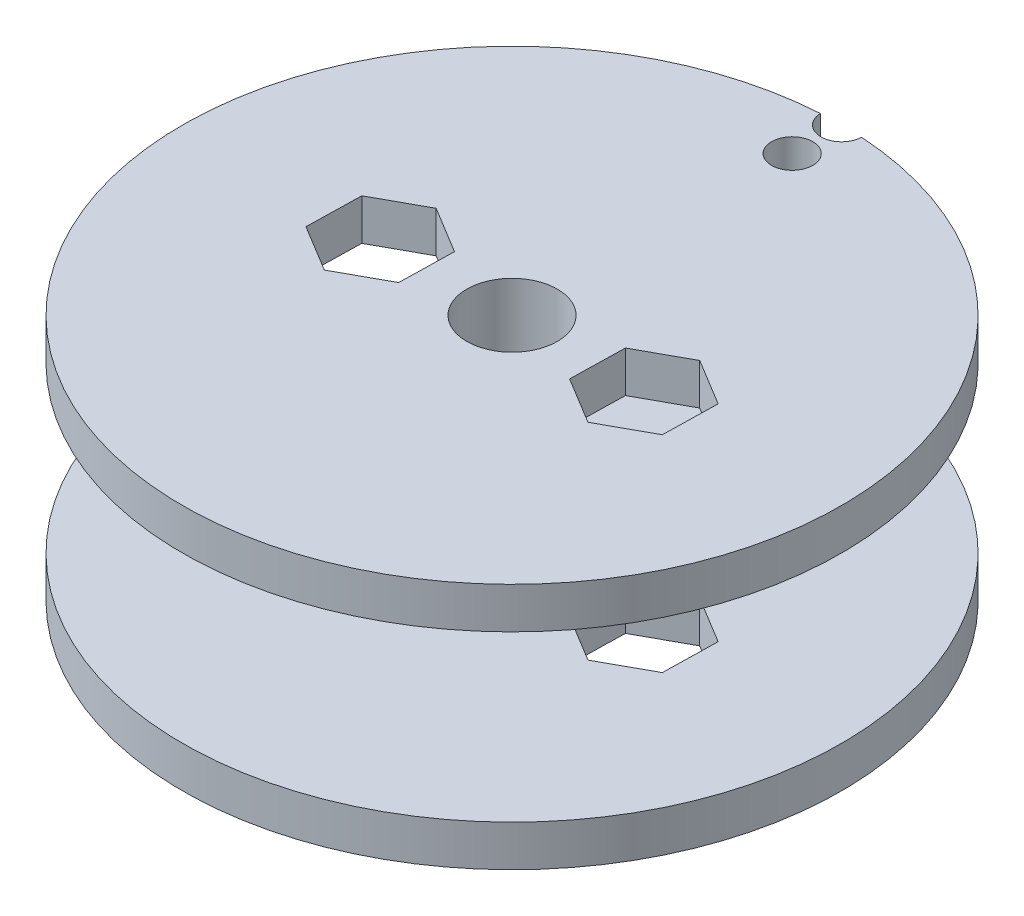
SolidWorks part; units mm, degrees
ref_plane "Front Plane" through (0, 0, 0) normal (0, 0, 1) x (1, 0, 0)
ref_plane "Top Plane" through (0, 0, 0) normal (0, 1, 0) x (1, 0, 0)
ref_plane "Right Plane" through (0, 0, 0) normal (1, 0, 0) x (0, 0, -1)
sketch "Sketch1" plane through (0, 0, 0) normal (0, 1, 0) x (1, 0, 0)
  circle A1 centre (0, 0) radius 20
  circle A2 centre (0, 0) radius 2.75
extrude "Boss-Extrude1" add sketch "Sketch1" along normal blind 2.5
sketch "Sketch2" plane through (0, 2.5, 0) normal (0, 1, 0) x (1, 0, 0)
  circle A0 centre (0, 0) radius 3
  circle A1 centre (0, 0) radius 2.75
sketch "Sketch3" plane through (0, 0, 0) normal (0, -1, 0) x (1, 0, 0)
  line L0 (-5.1613, 1.7213) -> (-8.0713, 3.319)
  line L1 (5.1613, -1.7213) -> (8.0713, -3.319)
  line L2 (8.0713, -3.319) -> (10.91, -1.5977)
  line L3 (10.91, -1.5977) -> (10.8387, 1.7213)
  line L4 (10.8387, 1.7213) -> (7.9287, 3.319)
  line L5 (7.9287, 3.319) -> (5.09, 1.5977)
  line L6 (5.09, 1.5977) -> (5.1613, -1.7213)
  line L7 (-8.0713, 3.319) -> (-10.91, 1.5977)
  line L8 (-10.91, 1.5977) -> (-10.8387, -1.7213)
  line L9 (-10.8387, -1.7213) -> (-7.9287, -3.319)
  line L10 (-7.9287, -3.319) -> (-5.09, -1.5977)
  line L11 (-5.09, -1.5977) -> (-5.1613, 1.7213)
  circle A0 centre (8, 0) radius 2.875 construction
  point P17 (0, 0)
  dimension "D2" = 8
  dimension "D1" = 2
extrude "Cut-Extrude3" cut sketch "Sketch3" against normal blind 2.5
sketch "Sketch4" plane through (0, 2.5, 0) normal (0, 1, 0) x (1, 0, 0)
  circle A0 centre (0, 17) radius 1.25
  circle A1 centre (0, 20) radius 1.25
  circle A2 centre (0, 0) radius 20 construction
  dimension "D1" = 17
extrude "Cut-Extrude4" cut sketch "Sketch4" against normal blind 5
sketch "Sketch5" plane through (0, 2.5, 0) normal (0, 1, 0) x (1, 0, 0)
  circle A0 centre (0, -16.2068) radius 3.1
extrude "Cut-Extrude5" [suppressed] cut sketch "Sketch5" along normal blind 2.5 from surface
extrude "Boss-Extrude2" add sketch "Sketch2" along normal blind 5
mirror "Mirror7" about plane through (0, 7.5, 0) normal (0, 1, 0) of bodies 107
